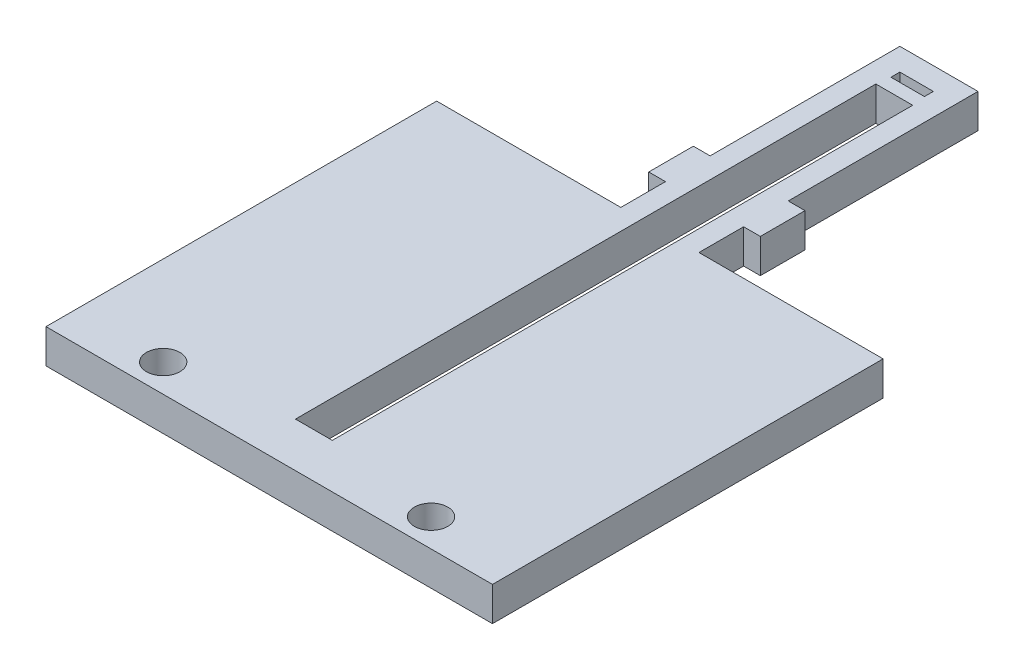
SolidWorks part; units mm, degrees
ref_plane "Front Plane" through (0, 0, 0) normal (0, 0, 1) x (1, 0, 0)
ref_plane "Top Plane" through (0, 0, 0) normal (0, 1, 0) x (1, 0, 0)
ref_plane "Right Plane" through (0, 0, 0) normal (1, 0, 0) x (0, 0, -1)
sketch "Sketch1" plane through (0, 0, 0) normal (0, 1, 0) x (1, 0, 0)
  line L1 (0, 0) -> (40, 0)
  line L2 (0, 0) -> (0, 60)
  line L3 (0, 60) -> (40, 60)
  line L4 (40, 0) -> (40, 60)
  dimension "D1" = 40
  dimension "D2" = 60
extrude "Boss-Extrude1" add sketch "Sketch1" along normal blind 3.05 contours L2 | L1 L4 L3 L2 | L4 region at (20, 0, -30)
sketch "Sketch4" plane through (0, 3.05, 0) normal (0, 1, 0) x (1, 0, 0)
  line L0 (20, 60) -> (20, 58)
  line L1 (0, 60) -> (40, 60) construction
  line L3 (21.5, 58) -> (18.5, 58)
  line L4 (18.5, 58) -> (18.5, 57.2)
  line L5 (18.5, 57.2) -> (21.5, 57.2)
  line L6 (21.5, 57.2) -> (21.5, 58)
  line L7 (20, 57.2) -> (20, 56)
  line L9 (21.65, 56) -> (18.35, 56)
  line L10 (18.35, 56) -> (18.35, 4)
  line L11 (18.35, 4) -> (21.65, 4)
  line L12 (21.65, 4) -> (21.65, 56)
  point P10 (20, 58)
  point P22 (20, 56)
  dimension "D1" = 2
  dimension "D2" = 0.8
  dimension "D3" = 1.2
  dimension "D4" = 3
  dimension "D5" = 52
  dimension "D6" = 3.3
extrude "Cut-Extrude1" cut sketch "Sketch4" against normal blind 10 contours L11 L12 L9 L10 | L5 L6 L3 L4 region at (20, 3.05, -57.6) region at (20, 3.05, -30)
sketch "Sketch5" plane through (0, 3.05, 0) normal (0, 1, 0) x (1, 0, 0)
  line L0 (0, 60) -> (0, 20)
  line L1 (0, 0) -> (0, 60) construction
  line L2 (0, 60) -> (15, 60)
  line L3 (0, 60) -> (40, 60) construction
  line L5 (40, 60) -> (25, 60)
  line L6 (40, 60) -> (40, 20)
  line L7 (40, 0) -> (40, 60) construction
  line L9 (15, 60) -> (15, 20)
  line L10 (15, 20) -> (0, 20)
  line L11 (25, 60) -> (25, 20)
  line L12 (25, 20) -> (40, 20)
  circle A0 centre (7.5, 27.5) radius 7.5
  circle A1 centre (32.5, 27.5) radius 7.5
  line M14 (40, 0) -> (40, 60)
  line M15 (40, 60) -> (0, 60)
  line M16 (0, 60) -> (0, 0)
  dimension "D1" = 40
  dimension "D2" = 15
  dimension "D3" = 40
  dimension "D4" = 15
extrude "Cut-Extrude2" [suppressed] cut sketch "Sketch5" against normal blind 10 contours A0 L9 M15 M16 | A0 | A0 L0 L10 | A1 L6 L11 M15 | A1 | A1 L12 M14
sketch "Sketch6" plane through (0, 3.05, 0) normal (0, 1, 0) x (1, 0, 0)
  line L0 (0, 60) -> (0, 35)
  line L1 (0, 0) -> (0, 60) construction
  line L2 (0, 60) -> (16.5, 60)
  line L3 (0, 60) -> (40, 60) construction
  line L4 (40, 60) -> (40, 35)
  line L5 (40, 0) -> (40, 60) construction
  line L6 (40, 60) -> (23.5, 60)
  line L9 (0, 35) -> (16.5, 35)
  line L12 (23.5, 35) -> (40, 35)
  line L13 (16.5, 35) -> (16.5, 39)
  line L14 (16.5, 39) -> (15, 39)
  line L15 (15, 39) -> (15, 43)
  line L16 (15, 43) -> (16.5, 43)
  line L17 (16.5, 43) -> (16.5, 60)
  line L18 (23.5, 35) -> (23.5, 39)
  line L19 (23.5, 39) -> (25, 39)
  line L20 (25, 39) -> (25, 43)
  line L21 (25, 43) -> (23.5, 43)
  line L22 (23.5, 43) -> (23.5, 60)
  dimension "D1" = 25
  dimension "D2" = 16.5
  dimension "D3" = 25
  dimension "D4" = 16.5
  dimension "D5" = 4
  dimension "D6" = 4
  dimension "D7" = 1.5
  dimension "D8" = 16.5
  dimension "D9" = 1.5
  dimension "D10" = 4
  dimension "D11" = 4
  dimension "D12" = 16.5
extrude "Cut-Extrude3" cut sketch "Sketch6" against normal blind 10
sketch "Sketch7" plane through (0, 3.05, 0) normal (0, 1, 0) x (1, 0, 0)
  line L0 (0, 0) -> (40, 0) construction
  line L1 (0, 0) -> (8, 0)
  line L2 (8, 0) -> (8, 2.5)
  line L3 (8, 2.5) -> (32, 2.5)
  circle A0 centre (8, 2.5) radius 1.5
  circle A1 centre (32, 2.5) radius 1.5
  dimension "D3" = 3
  dimension "D5" = 3
  dimension "D1" = 8
  dimension "D2" = 2.5
  dimension "D4" = 24
extrude "Cut-Extrude4" cut sketch "Sketch7" against normal blind 10 contours L3 A0 L2 | L2 A0 L3 | A1 region at (7.7878, 3.05, -2.7122) region at (32, 3.05, -3.9576) region at (8.6366, 3.05, -1.8634)
